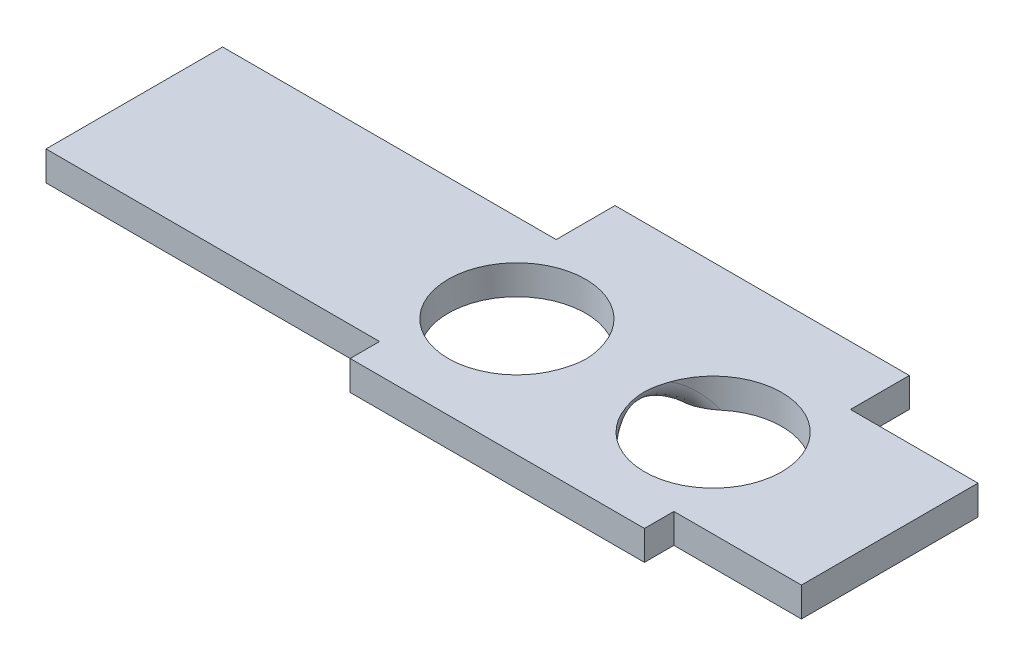
SolidWorks part; units mm, degrees
ref_plane "Front Plane" through (0, 0, 0) normal (0, 0, 1) x (1, 0, 0)
ref_plane "Top Plane" through (0, 0, 0) normal (0, 1, 0) x (1, 0, 0)
ref_plane "Right Plane" through (0, 0, 0) normal (1, 0, 0) x (0, 0, -1)
sketch "Sketch1" plane through (0, 0, 0) normal (0, 1, 0) x (1, 0, 0)
  line L0 (-3, 0) -> (-3, 50000) construction
  line L1 (3, 0) -> (3, 50000) construction
  line L2 (5, 0) -> (5, 50000) construction
  line L3 (-30.5, 9) -> (5.5, 9)
  line L4 (-30.5, 9) -> (-30.5, -9)
  line L5 (-30.5, -9) -> (5.5, -9)
  line L6 (5.5, 9) -> (5.5, -9) construction
  line L7 (-5, 0) -> (-5, 50000) construction
  line L9 (25.5, 9) -> (-10.5, 9)
  line L10 (25.5, 9) -> (25.5, -9)
  line L11 (25.5, -9) -> (-10.5, -9)
  line L12 (-10.5, 9) -> (-10.5, -9) construction
  line L13 (-30.5, 9) -> (25.5, 9)
  line L14 (-30.5, 9) -> (-30.5, -9)
  line L15 (-30.5, -9) -> (25.5, -9)
  line L16 (25.5, 9) -> (25.5, -9)
  circle A0 centre (0, 0) radius 3 construction
  circle A1 centre (-12.5, 0) radius 7
  circle A2 centre (7.5, 0) radius 7
  circle A3 centre (-10, 0) radius 15 construction
  circle A4 centre (10, 0) radius 15 construction
  point P11 (-30.5, 0)
  point P18 (-12.5, 9)
  point P25 (9.3539, 9)
  point P26 (7.5, 9)
  point P28 (25.5, 0)
  dimension "D1" = 6
  dimension "D2" = 36
  dimension "D5" = 14
  dimension "D6" = 14
  dimension "D9" = 2
  dimension "D7" = 2
  dimension "D8" = 7
  dimension "D10" = 12.5
  dimension "D3" = 7
  dimension "D4" = 18
  dimension "D11" = 7.5
  dimension "D12" = 36
extrude "BaseShape" add sketch "Sketch1" along normal blind 3 contours A2 | L14 L13 L16 L15 | A1 region at (7.5, 0, 0)
sketch "Sketch2" plane through (0, 0, 0) normal (0, -1, 0) x (1, 0, 0)
  line L0 (-30.5, -9) -> (25.5, -9) construction
  line L1 (-30.5, -9) -> (-51.5, -9)
  line L2 (-30.5, -9) -> (-30.5, 9)
  line L3 (-30.5, 9) -> (-51.5, 9)
  line L4 (-51.5, -9) -> (-51.5, 9)
  line L5 (-17.5, -9) -> (12.5, -9)
  line L6 (-17.5, -9) -> (-17.5, -15)
  line L7 (-17.5, -15) -> (12.5, -15)
  line L8 (12.5, -9) -> (12.5, -15)
  line L9 (-30.5, -9) -> (-17.5, -9) construction
  line L10 (12.5, -9) -> (25.5, -9) construction
  line L11 (-17.5, 9) -> (-17.5, 12)
  line L12 (-30.5, 9) -> (25.5, 9) construction
  line L13 (-17.5, 12) -> (12.5, 12)
  line L14 (12.5, 12) -> (12.5, 9)
  line L15 (12.5, 9) -> (-17.5, 9)
  dimension "D1" = 21
  dimension "D2" = 6
  dimension "D3" = 30
  dimension "D4" = 3
extrude "FingerJoints" add sketch "Sketch2" against normal up to surface (3 mm away) up to face at (-2.5, 3, 0)
ref_plane "Plane1" through (-5.5, 0, 0) normal (-1, 0, 0) x (0, 0, 1)
sketch "Sketch4" plane through (-5.5, 0, 0) normal (-1, 0, 0) x (0, 0, 1)
  line L0 (-4.1533, 0) -> (4.1533, 0)
  line L2 (0, 2.0241) -> (0, 50002.0241) construction
  arc A1 (4.1533, 0) -> (-4.1533, 0) centre (0, -5) ccw
  dimension "D1" = 13
  dimension "D2" = 5
extrude "Cut-Extrude1" cut sketch "Sketch4" against normal blind 10 from offset 2
fillet "Fillet1" radius 2 2 edges at (0.5274, 1.4705, -0.6191) (-5.5274, 1.4705, 0.6191)
